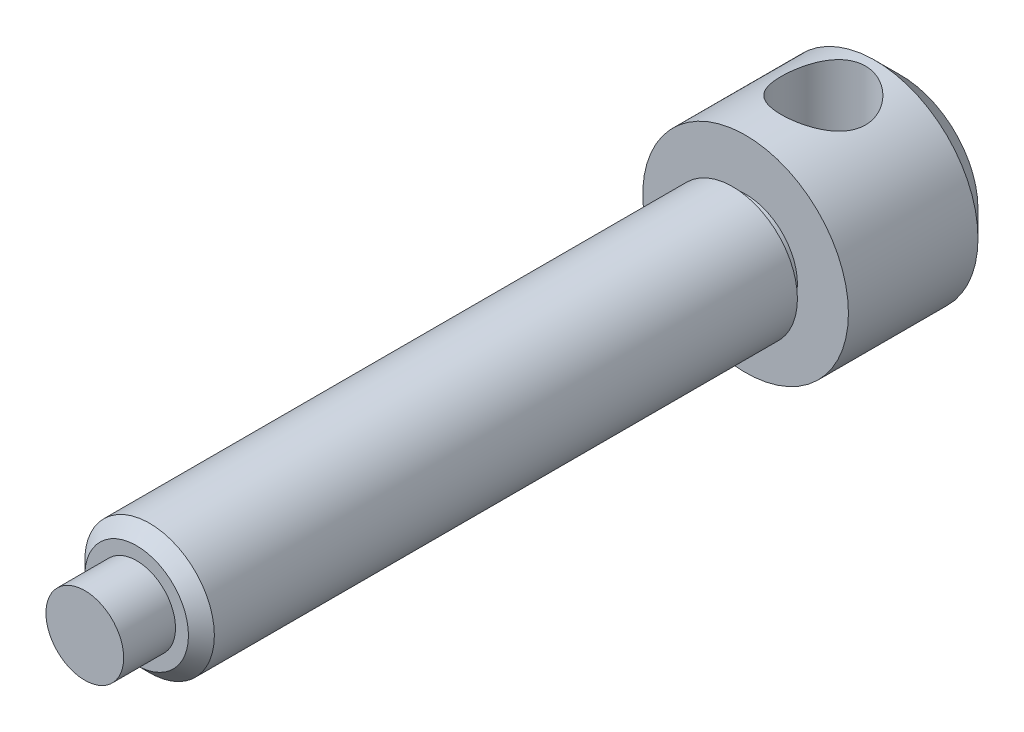
SolidWorks part; units mm, degrees
material "Cobre"
ref_plane "Plano frontal" through (0, 0, 0) normal (0, 0, 1) x (1, 0, 0)
ref_plane "Plano superior" through (0, 0, 0) normal (0, 1, 0) x (1, 0, 0)
ref_plane "Plano direito" through (0, 0, 0) normal (1, 0, 0) x (0, 0, -1)
sketch "Esboço1" plane through (0, 0, 0) normal (0, 0, 1) x (1, 0, 0)
  circle A0 centre (0, 0) radius 7.9375
  dimension "D1" = 15.875
extrude "Ressalto-extrusão1" add sketch "Esboço1" along normal blind 12
sketch "Esboço2" plane through (0, 0, 12) normal (0, 0, 1) x (1, 0, 0)
  circle A0 centre (0, 0) radius 4
  dimension "D1" = 8
extrude "Ressalto-extrusão2" add sketch "Esboço2" along normal blind 1
sketch "Esboço3" plane through (0, 0, 13) normal (0, 0, 1) x (1, 0, 0)
  circle A0 centre (0, 0) radius 5
  dimension "D1" = 10
extrude "Ressalto-extrusão3" add sketch "Esboço3" along normal blind 46
sketch "Esboço4" plane through (0, 0, 59) normal (0, 0, 1) x (1, 0, 0)
  circle A0 centre (0, 0) radius 3
  dimension "D1" = 6
extrude "Ressalto-extrusão4" add sketch "Esboço4" along normal blind 4
sketch "Esboço5" plane through (0, 0, 0) normal (0, 1, 0) x (1, 0, 0)
  circle A0 centre (0, -6) radius 3.25
  dimension "D3" = 6.5
  dimension "D1" = 0
  dimension "D2" = 6
extrude "Corte-extrusão1" cut sketch "Esboço5" against normal through all both and the other way through all
chamfer "Chanfro1" distance 2 angle 45 1 edges at (7.9375, 0, 0)
chamfer "Chanfro2" distance 1 angle 45 1 edges at (5, 0, 59)
